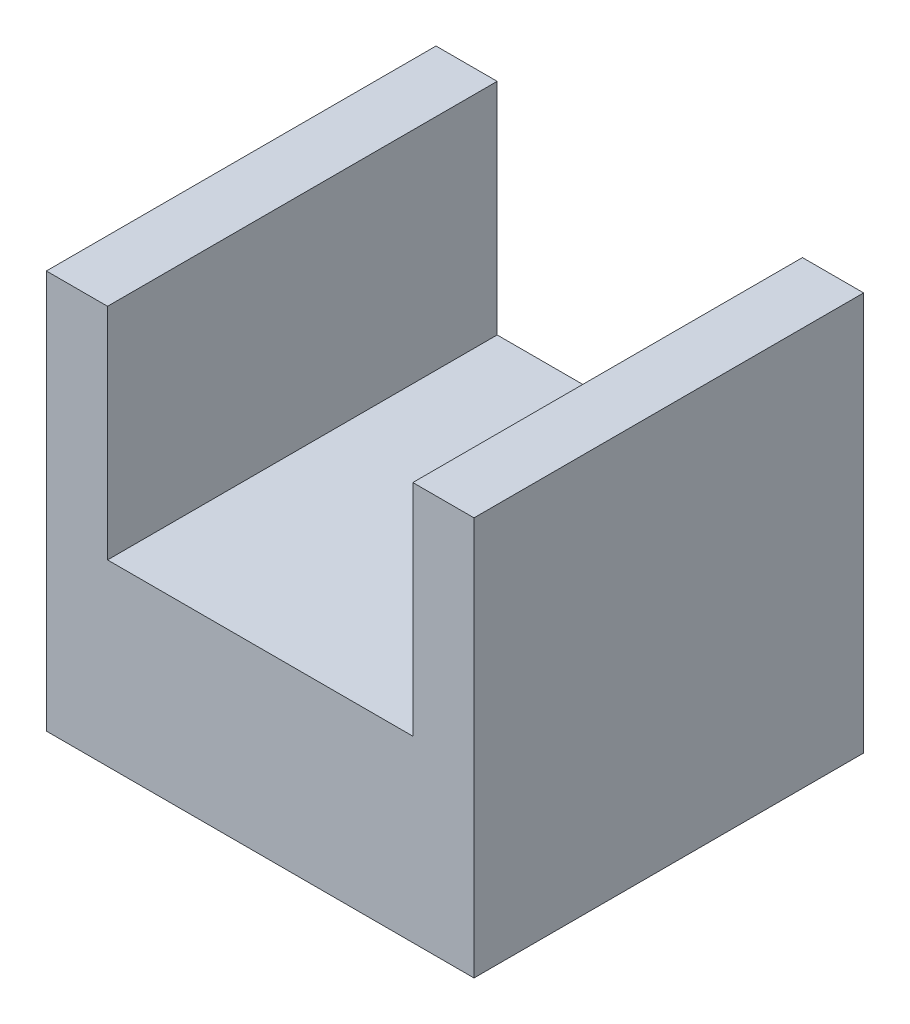
SolidWorks part; units mm, degrees
ref_plane "Front Plane" through (0, 0, 0) normal (0, 0, 1) x (1, 0, 0)
ref_plane "Top Plane" through (0, 0, 0) normal (0, 1, 0) x (1, 0, 0)
ref_plane "Right Plane" through (0, 0, 0) normal (1, 0, 0) x (0, 0, -1)
sketch "Sketch1" plane through (0, 0, 0) normal (0, 0, 1) x (1, 0, 0)
  line L1 (21.95, 20.455) -> (-21.95, 20.455)
  line L2 (21.95, 20.455) -> (21.95, -20.455)
  line L3 (21.95, -20.455) -> (-21.95, -20.455)
  line L4 (-21.95, 20.455) -> (-21.95, -20.455)
  line L5 (21.95, 20.455) -> (-21.95, -20.455) construction
  line L6 (21.95, -20.455) -> (-21.95, 20.455) construction
  point P0 (0, 0)
  dimension "D1" = 40.91
  dimension "D2" = 43.9
extrude "Boss-Extrude1" add sketch "Sketch1" along normal mid plane 40 contours L2 L1 L4 L3
sketch "Sketch2" plane through (0, 0, 20) normal (0, 0, 1) x (1, 0, 0)
  line L0 (-15.67, 20.455) -> (-15.67, -2.095)
  line L1 (21.95, 20.455) -> (-21.95, 20.455) construction
  line L2 (-15.67, -2.095) -> (15.67, -2.095)
  line L3 (-21.95, 20.455) -> (-21.95, -20.455) construction
  line L4 (0, -22) -> (0, 22) construction
  line L5 (15.67, 20.455) -> (15.67, -2.095)
  line L6 (15.67, 20.455) -> (-15.67, 20.455)
  point P12 (0, -2.095)
  dimension "D1" = 22.55
  dimension "D2" = 6.28
extrude "Cut-Extrude1" cut sketch "Sketch2" against normal up to next
ref_axis "Axis1" through (0, -22.5005, 0) along (0, 1, 0)
